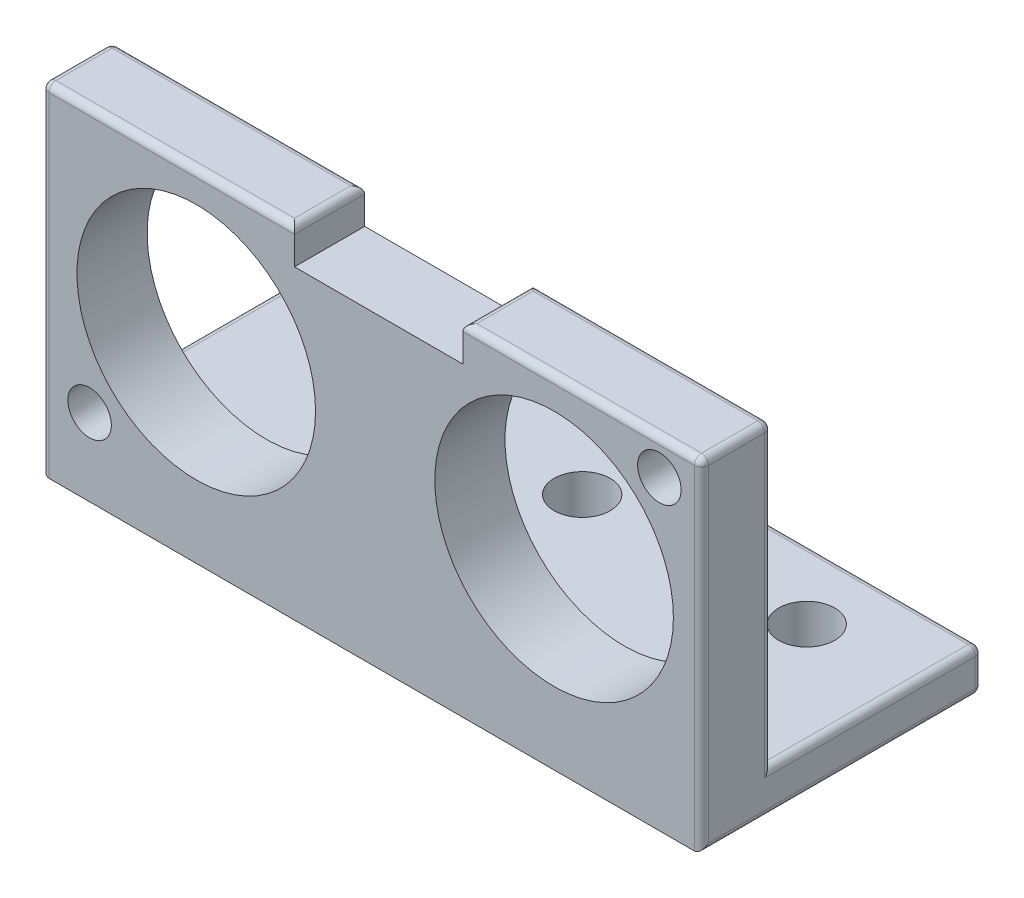
SolidWorks part; units mm, degrees
ref_plane "前基準面" through (0, 0, 0) normal (0, 0, 1) x (1, 0, 0)
ref_plane "上基準面" through (0, 0, 0) normal (0, 1, 0) x (1, 0, 0)
ref_plane "右基準面" through (0, 0, 0) normal (1, 0, 0) x (0, 0, -1)
sketch "草圖1" plane through (0, 0, 0) normal (0, 0, 1) x (1, 0, 0)
  line L1 (-23.5, 10.65) -> (23.5, 10.65)
  line L2 (-23.5, 10.65) -> (-23.5, -10.65)
  line L3 (-23.5, -10.65) -> (23.5, -10.65)
  line L4 (23.5, 10.65) -> (23.5, -10.65)
  line L5 (-23.5, 10.65) -> (23.5, -10.65) construction
  line L6 (-23.5, -10.65) -> (23.5, 10.65) construction
  point P0 (0, 0)
  dimension "D1" = 21.3
  dimension "D2" = 47
extrude "填料-伸長1" add sketch "草圖1" along normal blind 5
sketch "草圖2" plane through (0, 0, 5) normal (0, 0, 1) x (1, 0, 0)
  line L0 (-23.5, 10.65) -> (-23.5, -10.65) construction
  line L1 (-23.5, -10.65) -> (23.5, -10.65) construction
  line L2 (23.5, -10.65) -> (23.5, 10.65) construction
  line L3 (23.5, 10.65) -> (-23.5, 10.65) construction
  circle A0 centre (-20.1, -8.15) radius 1.55
  circle A1 centre (20.5, 8.15) radius 1.55
  circle A2 centre (-12.5, 0) radius 8.5
  circle A3 centre (13, 0) radius 8.5
  dimension "D1" = 3.1
  dimension "D4" = 3.1
  dimension "D6" = 2.5
  dimension "D7" = 17
  dimension "D8" = 17
  dimension "D2" = 3.4
  dimension "D3" = 2.5
  dimension "D5" = 3
  dimension "D9" = 11
  dimension "D10" = 10.5
extrude "除料-伸長1" cut sketch "草圖2" against normal blind 13.95 contours A1 | A3 | A0 | A2
sketch "草圖7" plane through (0, -10.65, 0) normal (0, -1, 0) x (1, 0, 0)
  line L0 (-23.5, 5) -> (-23.5, -15)
  line L1 (-23.5, -15) -> (23.5, -15)
  line L2 (23.5, -15) -> (23.5, 5)
  line L3 (23.5, 5) -> (-23.5, 5)
  line L4 (-23.5, 5) -> (23.5, 5) construction
  line L6 (23.5, 5) -> (23.5, 0) construction
  line L7 (-23.5, 5) -> (-23.5, 0) construction
  dimension "D1" = 20
extrude "填料-伸長3" add sketch "草圖7" along normal blind 3
sketch "草圖3" plane through (0, 0, 5) normal (0, 0, 1) x (1, 0, 0)
  line L1 (-5.5, 10.65) -> (6.5, 10.65)
  line L2 (-5.5, 10.65) -> (-5.5, 8.15)
  line L3 (-5.5, 8.15) -> (6.5, 8.15)
  line L4 (6.5, 10.65) -> (6.5, 8.15)
  line L5 (-5.5, 10.65) -> (6.5, 8.15) construction
  line L6 (-5.5, 8.15) -> (6.5, 10.65) construction
  line L8 (-23.5, 10.65) -> (-23.5, -13.65) construction
  line L10 (23.5, -13.65) -> (23.5, 10.65) construction
  line L11 (23.5, 10.65) -> (-23.5, 10.65) construction
  point P0 (0.5, 9.4)
  dimension "D1" = 18
  dimension "D2" = 17
  dimension "D3" = 2.5
extrude "除料-伸長2" cut sketch "草圖3" against normal blind 13.95
fillet "圓角4" radius 0.5 18 edges at (15, 10.65, 5) (6.5, 10.65, 2.5) (15, 10.65, 0) (-14.5, 10.65, 0) (-5.5, 10.65, 2.5) (-14.5, 10.65, 5) (-23.5, 10.65, 2.5) (-23.5, -1.5, 5) (-23.5, -13.65, -5) (-23.5, -12.15, -15) (23.5, -12.15, -15) (23.5, -13.65, -5) (23.5, -1.5, 5) (23.5, 10.65, 2.5)
sketch "草圖8" plane through (0, -10.65, 0) normal (0, 1, 0) x (1, 0, 0)
  line L0 (23.5, 14.5) -> (23.5, -0.5) construction
  line L2 (-23, 15) -> (23, 15) construction
  circle A0 centre (19.5, 10) radius 2
  dimension "D1" = 4
  dimension "D2" = 4
  dimension "D3" = 5
sketch "草圖9" plane through (0, -10.65, 0) normal (0, 1, 0) x (1, 0, 0)
  line L0 (0, 13.073) -> (0, -11.293) construction
  line L1 (28.6432, 0) -> (-30.902, 0) construction
sketch "草圖11" plane through (0, -10.65, 0) normal (0, 1, 0) x (1, 0, 0)
  line L0 (-5.5, -5) -> (-23, -5) construction
  circle A0 centre (0, 10) radius 2
  circle A1 centre (16, 10) radius 2
  circle A2 centre (-16, 10) radius 2
  dimension "D3" = 4
  dimension "D1" = 15
  dimension "D2" = 2
  dimension "D4" = 2
extrude "除料-伸長4" cut sketch "草圖11" against normal blind 3
fillet "圓角5" radius 0.5 6 edges at (-23.3536, -10.7964, -14.8536) (23.3536, -10.7964, -14.8536) (-23.3536, -13.5036, -14.8536) (23.3536, -13.5036, -14.8536) (0, -10.65, -15) (0, -13.65, -15)
